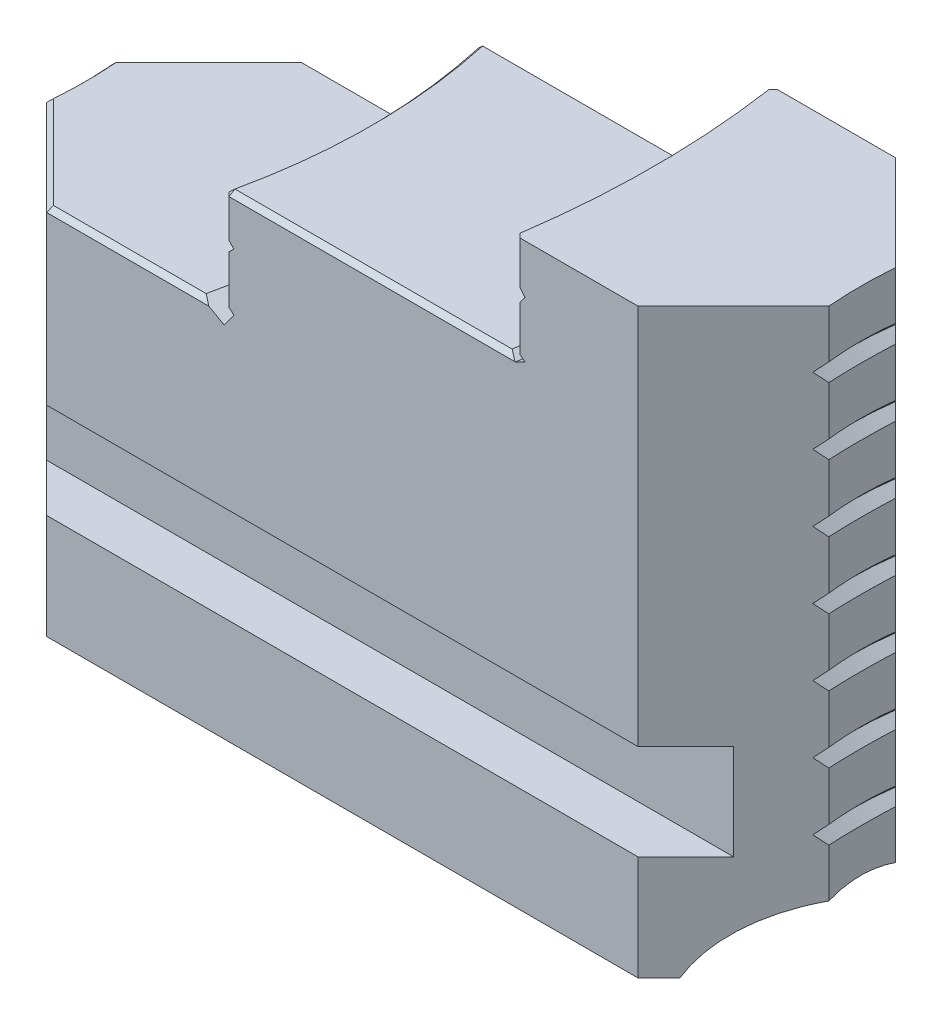
SolidWorks part; units mm, degrees
note: The reader was unsure of these and kept them because the rebuilt part matched: shared geometry of "Sketch24<2>".
material "AISI 4340 Steel, normalized"
ref_plane "Front Plane" through (0, 0, 0) normal (0, 0, 1) x (1, 0, 0)
ref_plane "Top Plane" through (0, 0, 0) normal (0, 1, 0) x (1, 0, 0)
ref_plane "Right Plane" through (0, 0, 0) normal (1, 0, 0) x (0, 0, -1)
sketch "Sketch1" plane through (0, 0, 0) normal (0, 1, 0) x (1, 0, 0)
  line L0 (0, -55) -> (0, 55) construction
  line L1 (-41, 13.485) -> (41, 13.485)
  line L2 (-41, 13.485) -> (-41, -13.485)
  line L3 (-41, -13.485) -> (41, -13.485)
  line L4 (41, 13.485) -> (41, -13.485)
  line L5 (-55, 0) -> (55, 0) construction
  dimension "D1" = 82
  dimension "D2" = 26.97
  dimension "D3" = 41
  dimension "D4" = 13.485
extrude "Boss-Extrude1" add sketch "Sketch1" along normal blind 61
chamfer "Chamfer1" distance 10 angle 45 4 edges at (41, 30.5, 13.485) (41, 30.5, -13.485) (-41, 30.5, -13.485) (-41, 30.5, 13.485)
sketch "Sketch2" plane through (0, 61, 0) normal (0, 1, 0) x (1, 0, 0)
  line L0 (0, 0) -> (83.1461, 0) construction
  line L1 (-33.55, 0) -> (33.55, 0) construction
  circle A0 centre (83.1461, 0) radius 42.2899
extrude "Cut-Extrude1" cut sketch "Sketch2" against normal through all
mirror "Mirror1" about plane through (0, 0, 0) normal (1, 0, 0) of "Cut-Extrude1"
sketch "Sketch19" plane through (0, 0, 0) normal (0, 0, 1) x (1, 0, 0)
  line L0 (40.8562, 56) -> (39.8562, 55)
  line L1 (39.8562, 55) -> (40.8562, 54)
  line L2 (40.8562, 54) -> (40.8562, 56)
  line L3 (39.8562, 55) -> (40.8562, 55) construction
  line L4 (40.8562, 61) -> (40.8562, 0) construction
  line L5 (41, 61) -> (31, 61) construction
  dimension "D1" = 0
  dimension "D2" = 1
  dimension "D3" = 6
revolve "Cut-Revolve3" cut sketch "Sketch19" angle 360 about L0
pattern_linear "LPattern1" count 8 spacing 7 along (0, -1, 0) of "Cut-Revolve3"
mirror "Mirror2" about plane through (0, 0, 0) normal (1, 0, 0) of "LPattern1", "Cut-Revolve3"
sketch "Sketch20" plane through (0, 0, 0) normal (0, 0, 1) x (1, 0, 0)
  line L0 (19.1438, 61) -> (19.1438, 57.1717)
  line L1 (31, 61) -> (-31, 61) construction
  line L2 (18.2525, 50.0025) -> (-10.8562, 50.0025)
  line L3 (-10.8562, 50.0025) -> (-10.8562, 46.0025)
  line L4 (-13.2922, 39.0025) -> (-40.8562, 39.0025)
  line L5 (-40.8562, 35) -> (-40.8562, 40) construction
  line L7 (-40.8562, 61) -> (19.1438, 61)
  line L8 (19.1438, 57.1717) -> (20.1438, 55.8476)
  line L9 (20.1438, 55.8476) -> (19.1438, 54.5236)
  line L10 (20.1438, 55.8476) -> (19.1438, 55.8476) construction
  line L11 (19.1438, 50.8416) -> (20.1438, 50.0025)
  line L12 (20.1438, 50.0025) -> (19.1438, 49.4879)
  line L13 (19.1438, 49.4879) -> (18.2525, 50.0025)
  line L14 (-70.8562, 71.8307) -> (-70.8562, 23.189) construction
  line L15 (-10.8562, 46.0025) -> (-9.8562, 45.0025)
  line L16 (-9.8562, 45.0025) -> (-10.8562, 44.0025)
  line L17 (-9.8562, 45.0025) -> (-10.8562, 45.0025) construction
  line L18 (-10.8562, 44.0025) -> (-10.8562, 39.8416)
  line L19 (19.1438, 54.5236) -> (19.1438, 50.8416)
  line L20 (-10.8562, 39.8416) -> (-9.8562, 39.0025)
  line L21 (-9.8562, 39.0025) -> (-10.8562, 37.596)
  line L22 (-10.8562, 37.596) -> (-13.2922, 39.0025)
  line L23 (-40.8562, 39.0025) -> (-40.8562, 61)
  dimension "D1" = 1
  dimension "D2" = 10
  dimension "D3" = 1
  dimension "D4" = 40
  dimension "D5" = 10.9975
  dimension "D6" = 11
  dimension "D7" = 90
  dimension "D8" = 30
  dimension "D9" = 60
  dimension "D10" = 5
  dimension "D11" = 90
  dimension "D12" = 1
  dimension "D13" = 10
  dimension "D14" = 1
  dimension "D15" = 40
revolve "Cut-Revolve4" cut sketch "Sketch20" angle 360 about L14
chamfer "Chamfer2" distance 0.5 angle 45 16 edges at (18.1279, 59.0859, -13.485) (18.1279, 52.6826, -13.485) (18.1279, 59.0859, 13.485) (18.1279, 52.6826, 13.485) (2.4175, 50.0025, 13.485) (2.4175, 50.0025, -13.485) (-10.8562, 50.0025, 0) (-12.3912, 48.0025, -13.485) (-12.3912, 41.9221, -13.485) (-12.3912, 48.0025, 13.485) (-12.3912, 41.9221, 13.485) (-22.947, 39.0025, -13.485) (-36, 39.0025, -8.485) (-40.8562, 39.0025, 0) (-36, 39.0025, 8.485) (-22.947, 39.0025, 13.485)
ref_plane "Plane1" through (-41, 0, 0) normal (1, 0, 0) x (0, 0, -1)
sketch "Sketch23" plane through (-41, 0, 0) normal (1, 0, 0) x (0, 0, -1)
  line L0 (0, 0) -> (0, 67.3666) construction
  line L1 (13.485, 0) -> (13.485, 38.5025) construction
  line L2 (13.485, 21.01) -> (8.475, 21.01)
  line L3 (13.485, 21.01) -> (13.485, 11)
  line L4 (13.485, 11) -> (8.475, 11)
  line L5 (8.475, 21.01) -> (8.475, 11)
  line L6 (3.485, 0) -> (13.485, 0) construction
  line L7 (-13.485, 21.01) -> (-13.485, 11)
  line L8 (-13.485, 11) -> (-8.475, 11)
  line L9 (-8.475, 21.01) -> (-8.475, 11)
  line L10 (-13.485, 21.01) -> (-8.475, 21.01)
  circle A0 centre (0, -4.75) radius 10
  dimension "D4" = 20
  dimension "D1" = 5.01
  dimension "D2" = 10.01
  dimension "D3" = 11
  dimension "D5" = 15.75
extrude "Cut-Extrude2" cut sketch "Sketch23" along normal blind 100
sketch "Sketch24" plane through (-41, 0, 0) normal (1, 0, 0) x (0, 0, -1)
  circle A0 centre (0, -4.75) radius 12.25
  dimension "D1" = 24.5
extrude "Cut-Extrude3" cut sketch "Sketch24" along normal blind 10
extrude "Cut-Extrude4" cut sketch "Sketch24<2>" against normal blind 10 from vertex at 82 starting at point (41, 6.9411, -3.485)
sketch "Sketch24<2>" plane through (-41, 0, 0) normal (1, 0, 0) x (0, 0, -1) same geometry as "Sketch24"
sketch "Sketch25" plane through (-41, 0, 0) normal (1, 0, 0) x (0, 0, -1)
  circle A1 centre (0, -4.75) radius 12.25
  circle A2 centre (0, -4.75) radius 12.25
  dimension "D1" = 0
curve "Helix/Spiral1" pitch 4 height 85.5 turns 21.375
sketch "Sketch26" plane through (0, 0, 0) normal (0, 0, 1) x (1, 0, 0)
  line L0 (-41, -14.8335) -> (-41, 14.8335) construction
  line L1 (-41, 7.5) -> (-43, 7.5)
  line L2 (-41, 7.5) -> (-41, 4.5)
  line L3 (-41, 4.5) -> (-43, 4.5)
  line L4 (-43, 7.5) -> (-43, 4.5)
  spline S0 degree 3 poles (-41, 7.5) (-40.9172, 7.5) (-40.7498, 6.8622) (-40.5001, 4.1376) (-40.25, 0.0599) (-40, -4.75) (-39.75, -9.5599) (-39.5, -13.6376) (-39.25, -16.3622) (-39, -17.3189) (-38.75, -16.3622) (-38.5, -13.6376) (-38.1667, -8.2007) (-37.8333, -1.2993) (-37.5, 4.1376) (-37.25, 6.8622) (-37, 7.8189) (-36.75, 6.8622) (-36.5, 4.1376) (-36.1667, -1.2993) (-35.8333, -8.2007) (-35.5, -13.6376) (-35.25, -16.3622) (-35, -17.3189) (-34.75, -16.3622) (-34.5, -13.6376) (-34.1667, -8.2007) (-33.8333, -1.2993) (-33.5, 4.1376) (-33.25, 6.8622) (-33, 7.8189) (-32.75, 6.8622) (-32.5, 4.1376) (-32.1667, -1.2993) (-31.8333, -8.2007) (-31.5, -13.6376) (-31.25, -16.3622) (-31, -17.3189) (-30.75, -16.3622) (-30.5, -13.6376) (-30.1667, -8.2007) (-29.8333, -1.2993) (-29.5, 4.1376) (-29.25, 6.8622) (-29, 7.8189) (-28.75, 6.8622) (-28.5, 4.1376) (-28.1667, -1.2993) (-27.8333, -8.2007) (-27.5, -13.6376) (-27.25, -16.3622) (-27, -17.3189) (-26.75, -16.3622) (-26.5, -13.6376) (-26.1667, -8.2007) (-25.8333, -1.2993) (-25.5, 4.1376) (-25.25, 6.8622) (-25, 7.8189) (-24.75, 6.8622) (-24.5, 4.1376) (-24.1667, -1.2993) (-23.8333, -8.2007) (-23.5, -13.6376) (-23.25, -16.3622) (-23, -17.3189) (-22.75, -16.3622) (-22.5, -13.6376) (-22.1667, -8.2007) (-21.8333, -1.2993) (-21.5, 4.1376) (-21.25, 6.8622) (-21, 7.8189) (-20.75, 6.8622) (-20.5, 4.1376) (-20.1667, -1.2993) (-19.8333, -8.2007) (-19.5, -13.6376) (-19.25, -16.3622) (-19, -17.3189) (-18.75, -16.3622) (-18.5, -13.6376) (-18.1667, -8.2007) (-17.8333, -1.2993) (-17.5, 4.1376) (-17.25, 6.8622) (-17, 7.8189) (-16.75, 6.8622) (-16.5, 4.1376) (-16.1667, -1.2993) (-15.8333, -8.2007) (-15.5, -13.6376) (-15.25, -16.3622) (-15, -17.3189) (-14.75, -16.3622) (-14.5, -13.6376) (-14.1667, -8.2007) (-13.8333, -1.2993) (-13.5, 4.1376) (-13.25, 6.8622) (-13, 7.8189) (-12.75, 6.8622) (-12.5, 4.1376) (-12.1667, -1.2993) (-11.8333, -8.2007) (-11.5, -13.6376) (-11.25, -16.3622) (-11, -17.3189) (-10.75, -16.3622) (-10.5, -13.6376) (-10.1667, -8.2007) (-9.8333, -1.2993) (-9.5, 4.1376) (-9.25, 6.8622) (-9, 7.8189) (-8.75, 6.8622) (-8.5, 4.1376) (-8.1667, -1.2993) (-7.8333, -8.2007) (-7.5, -13.6376) (-7.25, -16.3622) (-7, -17.3189) (-6.75, -16.3622) (-6.5, -13.6376) (-6.1667, -8.2007) (-5.8333, -1.2993) (-5.5, 4.1376) (-5.25, 6.8622) (-5, 7.8189) (-4.75, 6.8622) (-4.5, 4.1376) (-4.1667, -1.2993) (-3.8333, -8.2007) (-3.5, -13.6376) (-3.25, -16.3622) (-3, -17.3189) (-2.75, -16.3622) (-2.5, -13.6376) (-2.1667, -8.2007) (-1.8333, -1.2993) (-1.5, 4.1376) (-1.25, 6.8622) (-1, 7.8189) (-0.75, 6.8622) (-0.5, 4.1376) (-0.1667, -1.2993) (0.1667, -8.2007) (0.5, -13.6376) (0.75, -16.3622) (1, -17.3189) (1.25, -16.3622) (1.5, -13.6376) (1.8333, -8.2007) (2.1667, -1.2993) (2.5, 4.1376) (2.75, 6.8622) (3, 7.8189) (3.25, 6.8622) (3.5, 4.1376) (3.8333, -1.2993) (4.1667, -8.2007) (4.5, -13.6376) (4.75, -16.3622) (5, -17.3189) (5.25, -16.3622) (5.5, -13.6376) (5.8333, -8.2007) (6.1667, -1.2993) (6.5, 4.1376) (6.75, 6.8622) (7, 7.8189) (7.25, 6.8622) (7.5, 4.1376) (7.8333, -1.2993) (8.1667, -8.2007) (8.5, -13.6376) (8.75, -16.3622) (9, -17.3189) (9.25, -16.3622) (9.5, -13.6376) (9.8333, -8.2007) (10.1667, -1.2993) (10.5, 4.1376) (10.75, 6.8622) (11, 7.8189) (11.25, 6.8622) (11.5, 4.1376) (11.8333, -1.2993) (12.1667, -8.2007) (12.5, -13.6376) (12.75, -16.3622) (13, -17.3189) (13.25, -16.3622) (13.5, -13.6376) (13.8333, -8.2007) (14.1667, -1.2993) (14.5, 4.1376) (14.75, 6.8622) (15, 7.8189) (15.25, 6.8622) (15.5, 4.1376) (15.8333, -1.2993) (16.1667, -8.2007) (16.5, -13.6376) (16.75, -16.3622) (17, -17.3189) (17.25, -16.3622) (17.5, -13.6376) (17.8333, -8.2007) (18.1667, -1.2993) (18.5, 4.1376) (18.75, 6.8622) (19, 7.8189) (19.25, 6.8622) (19.5, 4.1376) (19.8333, -1.2993) (20.1667, -8.2007) (20.5, -13.6376) (20.75, -16.3622) (21, -17.3189) (21.25, -16.3622) (21.5, -13.6376) (21.8333, -8.2007) (22.1667, -1.2993) (22.5, 4.1376) (22.75, 6.8622) (23, 7.8189) (23.25, 6.8622) (23.5, 4.1376) (23.8333, -1.2993) (24.1667, -8.2007) (24.5, -13.6376) (24.75, -16.3622) (25, -17.3189) (25.25, -16.3622) (25.5, -13.6376) (25.8333, -8.2007) (26.1667, -1.2993) (26.5, 4.1376) (26.75, 6.8622) (27, 7.8189) (27.25, 6.8622) (27.5, 4.1376) (27.8333, -1.2993) (28.1667, -8.2007) (28.5, -13.6376) (28.75, -16.3622) (29, -17.3189) (29.25, -16.3622) (29.5, -13.6376) (29.8333, -8.2007) (30.1667, -1.2993) (30.5, 4.1376) (30.75, 6.8622) (31, 7.8189) (31.25, 6.8622) (31.5, 4.1376) (31.8333, -1.2993) (32.1667, -8.2007) (32.5, -13.6376) (32.75, -16.3622) (33, -17.3189) (33.25, -16.3622) (33.5, -13.6376) (33.8333, -8.2007) (34.1667, -1.2993) (34.5, 4.1376) (34.75, 6.8622) (35, 7.8189) (35.25, 6.8622) (35.5, 4.1376) (35.8333, -1.2993) (36.1667, -8.2007) (36.5, -13.6376) (36.75, -16.3622) (37, -17.3189) (37.25, -16.3622) (37.5, -13.6376) (37.8333, -8.2007) (38.1667, -1.2993) (38.5, 4.1376) (38.75, 6.8622) (39, 7.8189) (39.25, 6.8622) (39.5, 4.1376) (39.8333, -1.2993) (40.1667, -8.2007) (40.5, -13.6376) (40.75, -16.3622) (41, -17.3189) (41.25, -16.3622) (41.5, -13.6376) (41.8333, -8.2007) (42.1667, -1.2993) (42.5, 4.1376) (42.75, 6.8622) (43, 7.8189) (43.25, 6.8622) (43.5, 4.1375) (43.75, 0.0602) (44.0001, -4.7509) (44.2498, -9.5566) (44.4172, -12.2854) (44.5, -13.4121) knots 0 0 0 0 0.002924 0.005848 0.008772 0.011696 0.01462 0.017544 0.020468 0.023392 0.026316 0.02924 0.032164 0.038012 0.040936 0.04386 0.046784 0.049708 0.052632 0.055556 0.061404 0.064327 0.067251 0.070175 0.073099 0.076023 0.078947 0.084795 0.087719 0.090643 0.093567 0.096491 0.099415 0.102339 0.108187 0.111111 0.114035 0.116959 0.119883 0.122807 0.125731 0.131579 0.134503 0.137427 0.140351 0.143275 0.146199 0.149123 0.154971 0.157895 0.160819 0.163743 0.166667 0.169591 0.172515 0.178363 0.181287 0.184211 0.187135 0.190058 0.192982 0.195906 0.201754 0.204678 0.207602 0.210526 0.21345 0.216374 0.219298 0.225146 0.22807 0.230994 0.233918 0.236842 0.239766 0.24269 0.248538 0.251462 0.254386 0.25731 0.260234 0.263158 0.266082 0.27193 0.274854 0.277778 0.280702 0.283626 0.28655 0.289474 0.295322 0.298246 0.30117 0.304094 0.307018 0.309942 0.312865 0.318713 0.321637 0.324561 0.327485 0.330409 0.333333 0.336257 0.342105 0.345029 0.347953 0.350877 0.353801 0.356725 0.359649 0.365497 0.368421 0.371345 0.374269 0.377193 0.380117 0.383041 0.388889 0.391813 0.394737 0.397661 0.400585 0.403509 0.406433 0.412281 0.415205 0.418129 0.421053 0.423977 0.426901 0.429825 0.435673 0.438596 0.44152 0.444444 0.447368 0.450292 0.453216 0.459064 0.461988 0.464912 0.467836 0.47076 0.473684 0.476608 0.482456 0.48538 0.488304 0.491228 0.494152 0.497076 0.5 0.505848 0.508772 0.511696 0.51462 0.517544 0.520468 0.523392 0.52924 0.532164 0.535088 0.538012 0.540936 0.54386 0.546784 0.552632 0.555556 0.55848 0.561404 0.564327 0.567251 0.570175 0.576023 0.578947 0.581871 0.584795 0.587719 0.590643 0.593567 0.599415 0.602339 0.605263 0.608187 0.611111 0.614035 0.616959 0.622807 0.625731 0.628655 0.631579 0.634503 0.637427 0.640351 0.646199 0.649123 0.652047 0.654971 0.657895 0.660819 0.663743 0.669591 0.672515 0.675439 0.678363 0.681287 0.684211 0.687135 0.692982 0.695906 0.69883 0.701754 0.704678 0.707602 0.710526 0.716374 0.719298 0.722222 0.725146 0.72807 0.730994 0.733918 0.739766 0.74269 0.745614 0.748538 0.751462 0.754386 0.75731 0.763158 0.766082 0.769006 0.77193 0.774854 0.777778 0.780702 0.78655 0.789474 0.792398 0.795322 0.798246 0.80117 0.804094 0.809942 0.812865 0.815789 0.818713 0.821637 0.824561 0.827485 0.833333 0.836257 0.839181 0.842105 0.845029 0.847953 0.850877 0.856725 0.859649 0.862573 0.865497 0.868421 0.871345 0.874269 0.880117 0.883041 0.885965 0.888889 0.891813 0.894737 0.897661 0.903509 0.906433 0.909357 0.912281 0.915205 0.918129 0.921053 0.926901 0.929825 0.932749 0.935673 0.938596 0.94152 0.944444 0.950292 0.953216 0.95614 0.959064 0.961988 0.964912 0.967836 0.973684 0.976608 0.979532 0.982456 0.98538 0.988304 0.991228 0.994152 0.997076 1 1 1 1 construction
  dimension "D1" = 2
  dimension "D2" = 3
sweep "Cut-Sweep1" cut profiles "Sketch26" path "Helix/Spiral1"
